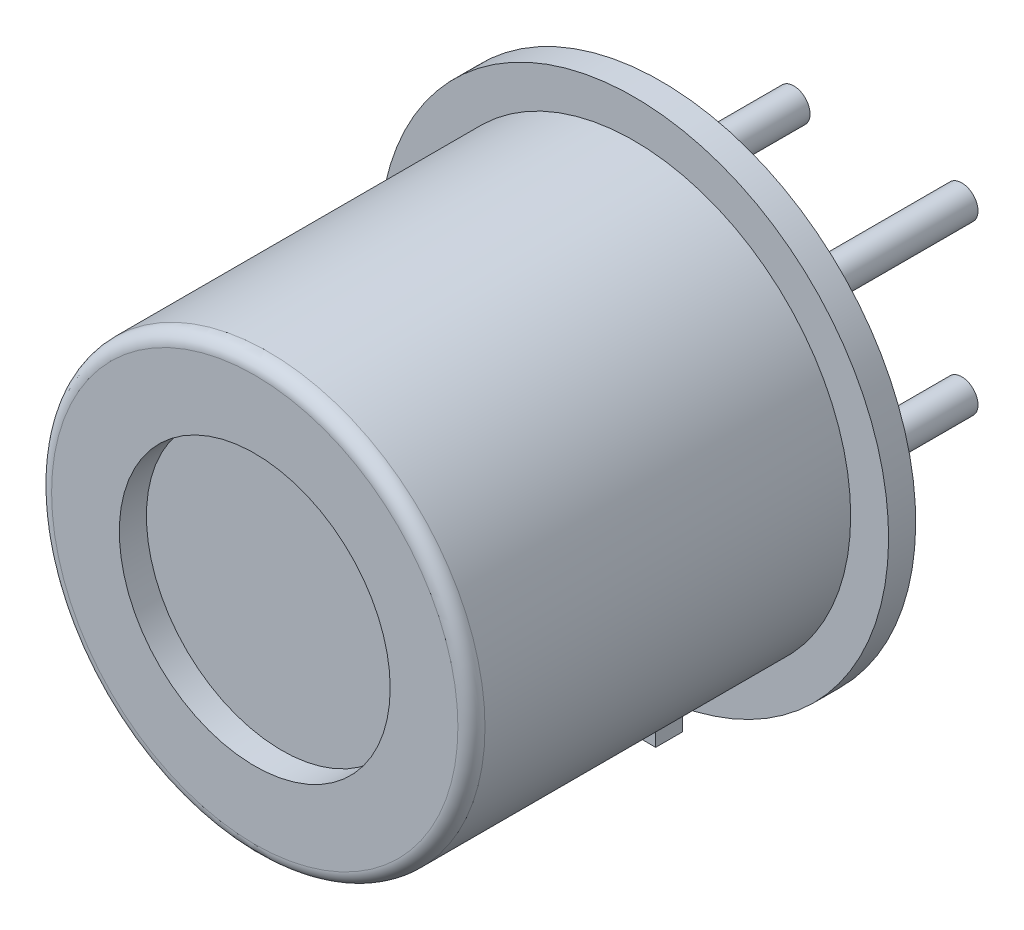
SolidWorks part; units mm, degrees
ref_plane "Front Plane" through (0, 0, 0) normal (0, 0, 1) x (1, 0, 0)
ref_plane "Top Plane" through (0, 0, 0) normal (0, 1, 0) x (1, 0, 0)
ref_plane "Right Plane" through (0, 0, 0) normal (1, 0, 0) x (0, 0, -1)
sketch "Sketch1" plane through (0, 0, 0) normal (0, 0, 1) x (1, 0, 0)
  circle A1 centre (-1.55, 1.55) radius 0.3
  circle A2 centre (-1.55, -1.55) radius 0.3
  circle A3 centre (1.55, 1.55) radius 0.3
  circle A4 centre (1.55, -1.55) radius 0.3
extrude "Boss-Extrude1" add sketch "Sketch1" along normal blind 2 and the other way blind 2
sketch "Sketch2" plane through (0, 0, 2) normal (0, 0, 1) x (1, 0, 0)
  line L2 (0, -5.5) -> (0.4, -5.5)
  line L3 (0, -5.5) -> (-0.4, -5.5)
  line L4 (-0.4, -5.5) -> (-0.4, -4.6829)
  line L5 (0.4, -5.5) -> (0.4, -4.6829)
  arc A0 (0.4, -4.6829) -> (-0.4, -4.6829) centre (0, 0) ccw
extrude "Boss-Extrude2" add sketch "Sketch2" along normal blind 0.5
sketch "Sketch3" plane through (0, 0, 2.5) normal (0, 0, 1) x (1, 0, 0)
  circle A0 centre (0, 0) radius 4
extrude "Boss-Extrude3" add sketch "Sketch3" along normal blind 7
fillet "Fillet1" radius 0.25 1 edges at (4, 0, 9.5)
sketch "Sketch4" plane through (0, 0, 9.5) normal (0, 0, 1) x (1, 0, 0)
  circle A0 centre (0, 0) radius 2.5
extrude "Cut-Extrude1" cut sketch "Sketch4" against normal blind 0.5
